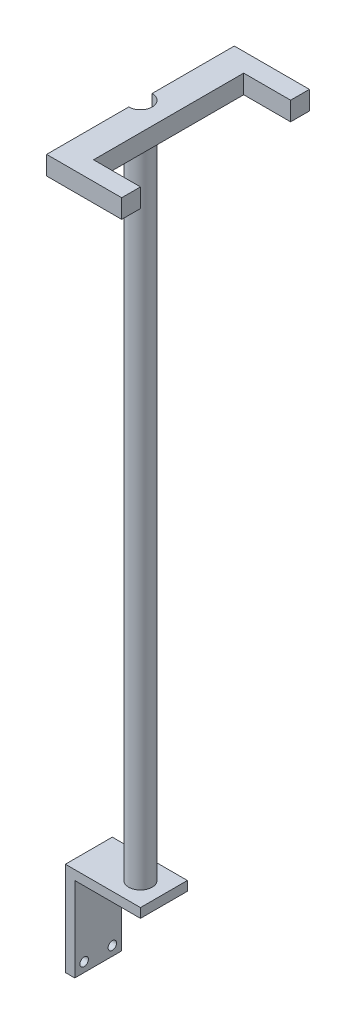
SolidWorks part; units mm, degrees
ref_plane "Płaszczyzna przednia" through (0, 0, 0) normal (0, 0, 1) x (1, 0, 0)
ref_plane "Płaszczyzna górna" through (0, 0, 0) normal (0, 1, 0) x (1, 0, 0)
ref_plane "Płaszczyzna prawa" through (0, 0, 0) normal (1, 0, 0) x (0, 0, -1)
sketch "Szkic1" plane through (0, 0, 0) normal (1, 0, 0) x (0, 0, -1)
  line L1 (0, 0) -> (50, 0)
  line L2 (0, 0) -> (0, 100)
  line L3 (0, 100) -> (50, 100)
  line L4 (50, 0) -> (50, 100)
  circle A0 centre (10, 10) radius 4.5
  circle A1 centre (40, 10) radius 4.5
  dimension "D1" = 9
  dimension "D2" = 9
  dimension "D3" = 50
  dimension "D4" = 100
  dimension "D5" = 10
  dimension "D6" = 10
  dimension "D7" = 10
  dimension "D8" = 10
extrude "Dodanie-wyciągnięcie1" add sketch "Szkic1" along normal blind 10
sketch "Szkic2" plane through (0, 0, -50) normal (0, 0, -1) x (-1, 0, 0)
  line L1 (0, 100) -> (-80, 100)
  line L2 (0, 100) -> (0, 90)
  line L3 (0, 90) -> (-80, 90)
  line L4 (-80, 100) -> (-80, 90)
  dimension "D1" = 10
  dimension "D2" = 80
extrude "Dodanie-wyciągnięcie2" add sketch "Szkic2" against normal blind 50
sketch "Szkic3" plane through (0, 100, 0) normal (0, 1, 0) x (1, 0, 0)
  line L0 (80, 0) -> (80, 50) construction
  line L1 (80, 0) -> (0, 0) construction
  circle A0 centre (55, 25) radius 12.5
  dimension "D1" = 25
  dimension "D2" = 25
  dimension "D3" = 25
extrude "Dodanie-wyciągnięcie3" add sketch "Szkic3" along normal blind 700
sketch "Szkic4" plane through (0, 800, 0) normal (0, 1, 0) x (1, 0, 0)
  line L1 (55, 125) -> (135, 125)
  line L2 (55, 125) -> (55, -75)
  line L3 (55, -75) -> (135, -75)
  line L4 (135, 125) -> (135, -75)
  line L5 (135, 105) -> (85, 105)
  line L6 (135, 105) -> (135, -55)
  line L7 (135, -55) -> (85, -55)
  line L8 (85, 105) -> (85, -55)
  circle M7 centre (55, 25) radius 12.5
  dimension "D1" = 200
  dimension "D2" = 80
  dimension "D3" = 20
  dimension "D4" = 20
  dimension "D5" = 30
extrude "Dodanie-wyciągnięcie4" add sketch "Szkic4" along normal blind 20 separate body contours L8 L5 L4 L1 L2 L3 L7 M7 region at (80.6234, 800, -25)
